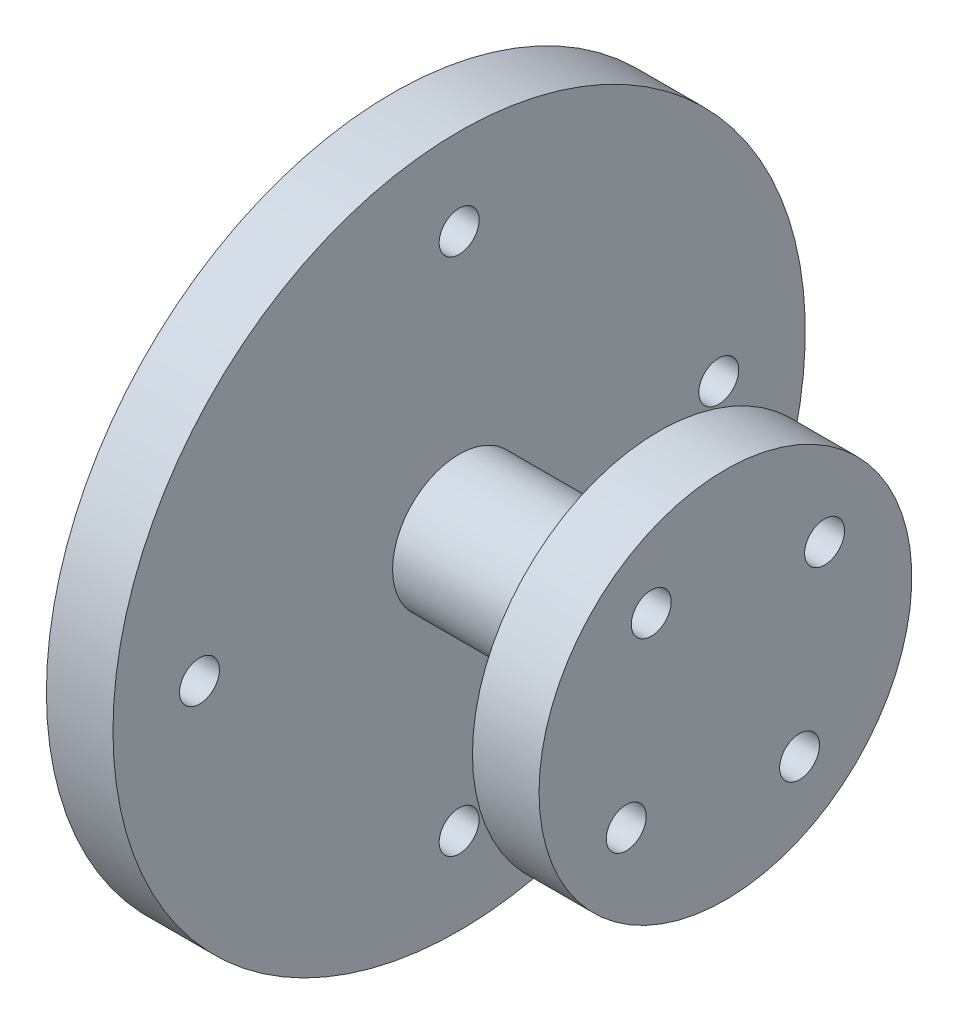
SolidWorks part; units mm, degrees
material "ABS"
ref_plane "Спереди" through (0, 0, 0) normal (0, 0, 1) x (1, 0, 0)
ref_plane "Сверху" through (0, 0, 0) normal (0, 1, 0) x (1, 0, 0)
ref_plane "Справа" through (0, 0, 0) normal (1, 0, 0) x (0, 0, -1)
sketch "Эскиз1" plane through (0, 0, 0) normal (0, 0, 1) x (1, 0, 0)
  line L0 (0, 0) -> (79.0641, 0) construction
  line L1 (0, 0) -> (0, 26)
  line L2 (0, 26) -> (5, 26)
  line L3 (5, 26) -> (5, 5)
  line L4 (5, 5) -> (20, 5)
  line L5 (20, 5) -> (20, 14)
  line L6 (20, 14) -> (25, 14)
  line L7 (25, 14) -> (25, 0)
  line L8 (0, 0) -> (25, 0)
  dimension "D1" = 52
  dimension "D2" = 28
  dimension "D3" = 5
  dimension "D4" = 15
  dimension "D5" = 5
  dimension "D6" = 10
revolve "Повернуть1" add sketch "Эскиз1" angle 360 about L0
sketch "Эскиз2" plane through (0, 0, 0) normal (-1, 0, 0) x (0, 0, 1)
  line L0 (50, 0) -> (-50, 0) construction
  circle A0 centre (0, 19.5) radius 1.5
  dimension "D1" = 3
  dimension "D2" = 19.5
  dimension "D3" = 19.5
extrude "Вырез-Вытянуть1" cut sketch "Эскиз2" against normal through all
ref_axis "Ось1" through (5, 0, 0) along (-1, 0, 0)
pattern_circular "Круговой массив1" count 4 over 360 about axis through (5, 0, 0) along (-1, 0, 0) of "Вырез-Вытянуть1"
sketch "Эскиз3" plane through (25, 0, 0) normal (1, 0, 0) x (0, 0, -1)
  circle A0 centre (7.4482, 5.5691) radius 1.5
  circle A2 centre (0, 0) radius 14 construction
  dimension "D1" = 3
  dimension "D2" = 9.3
  dimension "D3" = 7.4482
extrude "Вырез-Вытянуть2" cut sketch "Эскиз3" against normal up to next contours A0
pattern_circular "Круговой массив2" count 4 over 360 about axis through (5, 0, 0) along (-1, 0, 0) of "Вырез-Вытянуть2"
